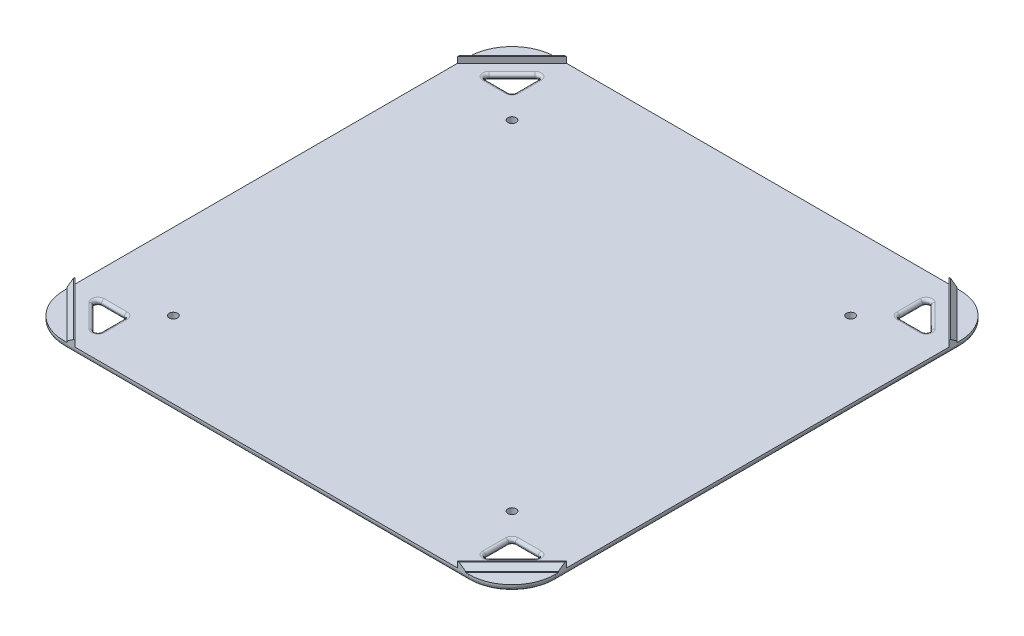
SolidWorks part; units mm, degrees
ref_plane "Front Plane" through (0, 0, 0) normal (0, 0, 1) x (1, 0, 0)
ref_plane "Top Plane" through (0, 0, 0) normal (0, 1, 0) x (1, 0, 0)
ref_plane "Right Plane" through (0, 0, 0) normal (1, 0, 0) x (0, 0, -1)
sketch "Sketch1" plane through (0, 0, 0) normal (0, 1, 0) x (1, 0, 0)
  line L5 (-134.62, -134.62) -> (134.62, -134.62)
  line L6 (-134.62, -134.62) -> (-134.62, 134.62)
  line L7 (-134.62, 134.62) -> (134.62, 134.62)
  line L8 (134.62, -134.62) -> (134.62, 134.62)
  line L9 (-134.62, -134.62) -> (134.62, 134.62) construction
  line L10 (-134.62, 134.62) -> (134.62, -134.62) construction
  point P0 (0, 0)
  dimension "D1" = 269.24
extrude "Boss-Extrude1" add sketch "Sketch1" along normal blind 3.175
fillet "Fillet1" radius 23.8125 4 edges at (134.62, 1.5875, 134.62) (134.62, 1.5875, -134.62) (-134.62, 1.5875, -134.62) (-134.62, 1.5875, 134.62)
fillet "Fillet2" radius 1.905 8 edges at (0, 0, -134.62) (127.6455, 0, -127.6455) (134.62, 0, 0) (127.6455, 0, 127.6455) (0, 0, 134.62) (-127.6455, 0, 127.6455) (-134.62, 0, 0) (-127.6455, 0, -127.6455)
sketch "Sketch9" plane through (0, 3.175, 0) normal (0, 1, 0) x (1, 0, 0)
  line L0 (134.62, -109.22) -> (109.22, -134.62)
  line L1 (109.22, -134.62) -> (104.7299, -134.62)
  line L2 (104.7299, -134.62) -> (134.62, -104.7299)
  line L3 (134.62, -104.7299) -> (134.62, -109.22)
  line L4 (-110.8075, -134.62) -> (110.8075, -134.62)
  line L5 (134.62, -110.8075) -> (134.62, 110.8075)
  line L6 (110.8075, 134.62) -> (-110.8075, 134.62)
  line L7 (-134.62, 110.8075) -> (-134.62, -110.8075)
  line L8 (-110.8075, -134.62) -> (110.8075, -134.62)
  line L9 (134.62, -110.8075) -> (134.62, 110.8075)
  line L10 (110.8075, 134.62) -> (-110.8075, 134.62)
  line L11 (-134.62, 110.8075) -> (-134.62, -110.8075)
  line L12 (-104.7299, -134.62) -> (-109.22, -134.62)
  line L13 (-109.22, -134.62) -> (-134.62, -109.22)
  line L14 (-134.62, -109.22) -> (-134.62, -104.7299)
  line L15 (-134.62, -104.7299) -> (-104.7299, -134.62)
  line L16 (-134.62, 104.7299) -> (-134.62, 109.22)
  line L17 (-134.62, 109.22) -> (-109.22, 134.62)
  line L18 (-109.22, 134.62) -> (-104.7299, 134.62)
  line L19 (-104.7299, 134.62) -> (-134.62, 104.7299)
  line L20 (104.7299, 134.62) -> (109.22, 134.62)
  line L21 (109.22, 134.62) -> (134.62, 109.22)
  line L22 (134.62, 109.22) -> (134.62, 104.7299)
  line L23 (134.62, 104.7299) -> (104.7299, 134.62)
  arc A4 (110.8075, -134.62) -> (134.62, -110.8075) centre (110.8075, -110.8075) ccw
  arc A5 (134.62, 110.8075) -> (110.8075, 134.62) centre (110.8075, 110.8075) ccw
  arc A6 (-110.8075, 134.62) -> (-134.62, 110.8075) centre (-110.8075, 110.8075) ccw
  arc A7 (-134.62, -110.8075) -> (-110.8075, -134.62) centre (-110.8075, -110.8075) ccw
  arc A8 (110.8075, -134.62) -> (134.62, -110.8075) centre (110.8075, -110.8075) ccw
  arc A9 (134.62, 110.8075) -> (110.8075, 134.62) centre (110.8075, 110.8075) ccw
  arc A10 (-110.8075, 134.62) -> (-134.62, 110.8075) centre (-110.8075, 110.8075) ccw
  arc A11 (-134.62, -110.8075) -> (-110.8075, -134.62) centre (-110.8075, -110.8075) ccw
  point P12 (134.62, 0)
  point P17 (0, -134.62)
  point P20 (0, 0)
  point P34 (0, 0)
  dimension "D2" = 25.4
  dimension "D3" = 25.4
  dimension "D4" = 3.175
  dimension "D5" = 4
  dimension "D6" = 25.4
  dimension "D7" = 25.4
  dimension "D1" = 0
extrude "Boss-Extrude2" add sketch "Sketch9" along normal blind 3.175 contours L19 L10 L17 L11 | L23 L9 L21 L10 | L13 L14 L15 L12 | L2 L3 L0 L1 region at (120.7671, 3.175, -120.7671) region at (-120.7671, 3.175, -120.7671)
sketch "Sketch8" plane through (0, 3.175, 0) normal (0, 1, 0) x (1, 0, 0)
  line L0 (-119.6749, -119.6749) -> (-92.7342, -92.7342)
  line L1 (-92.7342, 92.7342) -> (-119.6749, 119.6749)
  line L2 (119.6749, 119.6749) -> (92.7342, 92.7342)
  line L3 (92.7342, -92.7342) -> (119.6749, -119.6749)
  line L4 (-104.7299, -134.62) -> (104.7299, -134.62)
  line L5 (-104.7299, -134.62) -> (104.7299, -134.62)
  line L6 (104.7299, -134.62) -> (134.62, -104.7299)
  line L7 (104.7299, -134.62) -> (134.62, -104.7299)
  line L18 (134.62, -104.7299) -> (134.62, 104.7299)
  line L19 (134.62, -104.7299) -> (134.62, 104.7299)
  line L20 (134.62, 104.7299) -> (104.7299, 134.62)
  line L21 (134.62, 104.7299) -> (104.7299, 134.62)
  line L22 (104.7299, 134.62) -> (-104.7299, 134.62)
  line L23 (104.7299, 134.62) -> (-104.7299, 134.62)
  line L24 (-104.7299, 134.62) -> (-134.62, 104.7299)
  line L25 (-104.7299, 134.62) -> (-134.62, 104.7299)
  line L26 (-134.62, 104.7299) -> (-134.62, -104.7299)
  line L27 (-134.62, 104.7299) -> (-134.62, -104.7299)
  line L28 (-134.62, -104.7299) -> (-104.7299, -134.62)
  line L29 (-134.62, -104.7299) -> (-104.7299, -134.62)
  circle A0 centre (-92.7342, -92.7342) radius 2.286
  circle A4 centre (92.7342, -92.7342) radius 2.286
  circle A5 centre (-92.7342, 92.7342) radius 2.286
  circle A6 centre (92.7342, 92.7342) radius 2.286
  point P0 (-119.6749, -119.6749)
  point P1 (-119.6749, 119.6749)
  point P2 (-92.7342, -92.7342)
  point P4 (119.6749, 119.6749)
  point P5 (119.6749, -119.6749)
  point P7 (-92.7342, 119.6749)
  point P12 (119.6749, -92.7342)
  point P13 (119.6749, 119.6749)
  dimension "D2" = 4.572
  dimension "D3" = 90
  dimension "D4" = 38.1
  dimension "D5" = 90
  dimension "D6" = 90
  dimension "D7" = 90
  dimension "D1" = 0
extrude "Cut-Extrude4" cut sketch "Sketch8" against normal up to next contours A0 | A5 | A6 | A4
chamfer "Chamfer1" distance 2.54 4 edges at (-121.92, 6.35, 121.92) (-121.92, 6.35, -121.92) (121.92, 6.35, -121.92) (121.92, 6.35, 121.92)
sketch "Sketch10" plane through (0, 3.175, 0) normal (0, 1, 0) x (1, 0, 0)
  line L0 (-105.2108, -105.2108) -> (-124.2608, -105.2108)
  line L1 (-124.2608, -105.2108) -> (-105.2108, -124.2608)
  line L2 (-105.2108, -124.2608) -> (-105.2108, -105.2108)
  line L3 (-119.6749, -119.6749) -> (-114.7358, -114.7358)
  line L4 (-124.2608, 105.2108) -> (-105.2108, 105.2108)
  line L5 (-105.2108, 105.2108) -> (-105.2108, 124.2608)
  line L6 (-105.2108, 124.2608) -> (-124.2608, 105.2108)
  line L7 (-119.6749, 119.6749) -> (-114.7358, 114.7358)
  line L8 (-104.7299, -134.62) -> (104.7299, -134.62)
  line L9 (104.7299, -134.62) -> (134.62, -104.7299)
  line L10 (134.62, -104.7299) -> (134.62, 104.7299)
  line L11 (134.62, 104.7299) -> (104.7299, 134.62)
  line L12 (104.7299, 134.62) -> (-104.7299, 134.62)
  line L13 (-104.7299, 134.62) -> (-134.62, 104.7299)
  line L14 (-134.62, 104.7299) -> (-134.62, -104.7299)
  line L15 (-134.62, -104.7299) -> (-104.7299, -134.62)
  line L16 (-104.7299, -134.62) -> (104.7299, -134.62)
  line L17 (104.7299, -134.62) -> (134.62, -104.7299)
  line L18 (134.62, -104.7299) -> (134.62, 104.7299)
  line L19 (134.62, 104.7299) -> (104.7299, 134.62)
  line L20 (104.7299, 134.62) -> (-104.7299, 134.62)
  line L21 (-104.7299, 134.62) -> (-134.62, 104.7299)
  line L22 (-134.62, 104.7299) -> (-134.62, -104.7299)
  line L23 (-134.62, -104.7299) -> (-104.7299, -134.62)
  line L24 (105.2108, 124.2608) -> (105.2108, 105.2108)
  line L25 (105.2108, 105.2108) -> (124.2608, 105.2108)
  line L26 (124.2608, 105.2108) -> (105.2108, 124.2608)
  line L27 (119.6749, 119.6749) -> (114.7358, 114.7358)
  line L28 (124.2608, -105.2108) -> (105.2108, -105.2108)
  line L29 (105.2108, -105.2108) -> (105.2108, -124.2608)
  line L30 (105.2108, -124.2608) -> (124.2608, -105.2108)
  line L31 (119.6749, -119.6749) -> (114.7358, -114.7358)
  point P6 (-119.6749, -119.6749)
  point P10 (-114.7358, -114.7358)
  point P12 (-134.62, 0)
  point P14 (0, 134.62)
  point P19 (0, 0)
  point P24 (-119.6749, 119.6749)
  point P26 (-114.7358, 114.7358)
  point P31 (119.6749, 119.6749)
  point P33 (114.7358, 114.7358)
  point P38 (119.6749, -119.6749)
  point P40 (114.7358, -114.7358)
  point P43 (0, 0)
  dimension "D2" = 90
  dimension "D3" = 19.05
  dimension "D4" = 90
  dimension "D5" = 6.985
  dimension "D1" = 0
  dimension "D6" = 4
extrude "Cut-Extrude5" cut sketch "Sketch10" against normal up to next contours L1 L2 L0 | L5 L6 L4 | L25 L26 L24 | L29 L30 L28 region at (-111.5608, 3.175, 111.5608) region at (111.5608, 3.175, 111.5608) region at (111.5608, 3.175, -111.5608) region at (-111.5608, 3.175, -111.5608)
fillet "Fillet3" radius 1.905 12 edges at (105.2108, 1.5875, 105.2108) (124.2608, 1.5875, 105.2108) (105.2108, 1.5875, 124.2608) (105.2108, 1.5875, -124.2608) (124.2608, 1.5875, -105.2108) (105.2108, 1.5875, -105.2108) (-105.2108, 1.5875, -124.2608) (-105.2108, 1.5875, -105.2108) (-124.2608, 1.5875, -105.2108) (-105.2108, 1.5875, 105.2108) (-105.2108, 1.5875, 124.2608) (-124.2608, 1.5875, 105.2108)
fillet "Fillet4" radius 1.5875 24 edges at (-106.3868, 0, 121.4217) (-114.7358, 0, 114.7358) (-121.4217, 0, 106.3868) (-113.3888, 0, 105.2108) (-105.7688, 0, 105.7688) (-121.4217, 0, -106.3868) (-114.7358, 0, -114.7358) (-106.3868, 0, -121.4217) (-105.2108, 0, -113.3888) (-105.7688, 0, -105.7688) (105.7688, 0, -105.7688) (105.2108, 0, -113.3888) (106.3868, 0, -121.4217) (114.7358, 0, -114.7358) (121.4217, 0, -106.3868) (106.3868, 0, 121.4217) (105.2108, 0, 113.3888) (105.7688, 0, 105.7688) (113.3888, 0, 105.2108) (121.4217, 0, 106.3868) (-105.2108, 0, 113.3888) (-113.3888, 0, -105.2108) (113.3888, 0, -105.2108) (114.7358, 0, 114.7358)
fillet "Fillet5" radius 1.5875 24 edges at (105.7688, 3.175, 105.7688) (113.3888, 3.175, 105.2108) (121.4217, 3.175, 106.3868) (114.7358, 3.175, 114.7358) (106.3868, 3.175, 121.4217) (105.7688, 3.175, -105.7688) (105.2108, 3.175, -113.3888) (106.3868, 3.175, -121.4217) (114.7358, 3.175, -114.7358) (121.4217, 3.175, -106.3868) (-121.4217, 3.175, -106.3868) (-114.7358, 3.175, -114.7358) (-106.3868, 3.175, -121.4217) (-105.2108, 3.175, -113.3888) (-105.7688, 3.175, -105.7688) (-121.4217, 3.175, 106.3868) (-113.3888, 3.175, 105.2108) (-105.7688, 3.175, 105.7688) (-105.2108, 3.175, 113.3888) (-106.3868, 3.175, 121.4217) (105.2108, 3.175, 113.3888) (113.3888, 3.175, -105.2108) (-113.3888, 3.175, -105.2108) (-114.7358, 3.175, 114.7358)
